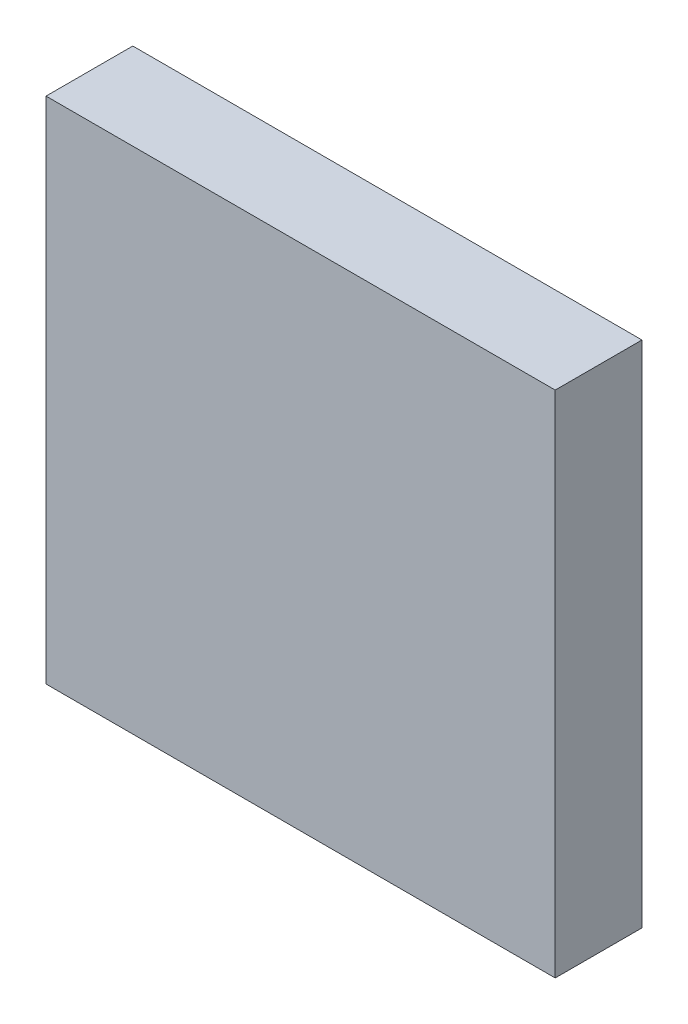
SolidWorks part; units mm, degrees
ref_plane "Ebene vorne" through (0, 0, 0) normal (0, 0, 1) x (1, 0, 0)
ref_plane "Ebene oben" through (0, 0, 0) normal (0, 1, 0) x (1, 0, 0)
ref_plane "Ebene rechts" through (0, 0, 0) normal (1, 0, 0) x (0, 0, -1)
sketch "Skizze1" plane through (0, 0, 0) normal (0, 0, 1) x (1, 0, 0)
  line L0 (67.5, 67.5) -> (-67.5, 67.5) construction
  line L1 (-67.5, 67.5) -> (-67.5, -67.5) construction
  line L2 (67.5, -67.5) -> (67.5, 67.5) construction
  line L3 (-67.5, -67.5) -> (67.5, -67.5) construction
  line L4 (67.5, 67.5) -> (-67.5, 67.5)
  line L5 (-67.5, 67.5) -> (-67.5, -67.5)
  line L6 (67.5, -67.5) -> (67.5, 67.5)
  line L7 (-67.5, -67.5) -> (67.5, -67.5)
  line L8 (65.5, 65.5) -> (-65.5, 65.5)
  line L9 (-65.5, 65.5) -> (-65.5, -65.5)
  line L10 (-65.5, -65.5) -> (65.5, -65.5)
  line L11 (65.5, -65.5) -> (65.5, 65.5)
  dimension "D1" = 2
extrude "Aufsatz-Linear austragen1" add sketch "Skizze1" along normal blind 18
sketch "Skizze2" plane through (0, 0, 18) normal (0, 0, 1) x (1, 0, 0)
  line L0 (-67.5, 67.5) -> (-67.5, -67.5) construction
  line L1 (-67.5, -67.5) -> (67.5, -67.5) construction
  line L2 (67.5, -67.5) -> (67.5, 67.5) construction
  line L3 (67.5, 67.5) -> (-67.5, 67.5) construction
  line L4 (-67.5, 67.5) -> (-67.5, -67.5)
  line L5 (-67.5, -67.5) -> (67.5, -67.5)
  line L6 (67.5, -67.5) -> (67.5, 67.5)
  line L7 (67.5, 67.5) -> (-67.5, 67.5)
extrude "Aufsatz-Linear austragen2" add sketch "Skizze2" along normal blind 5
